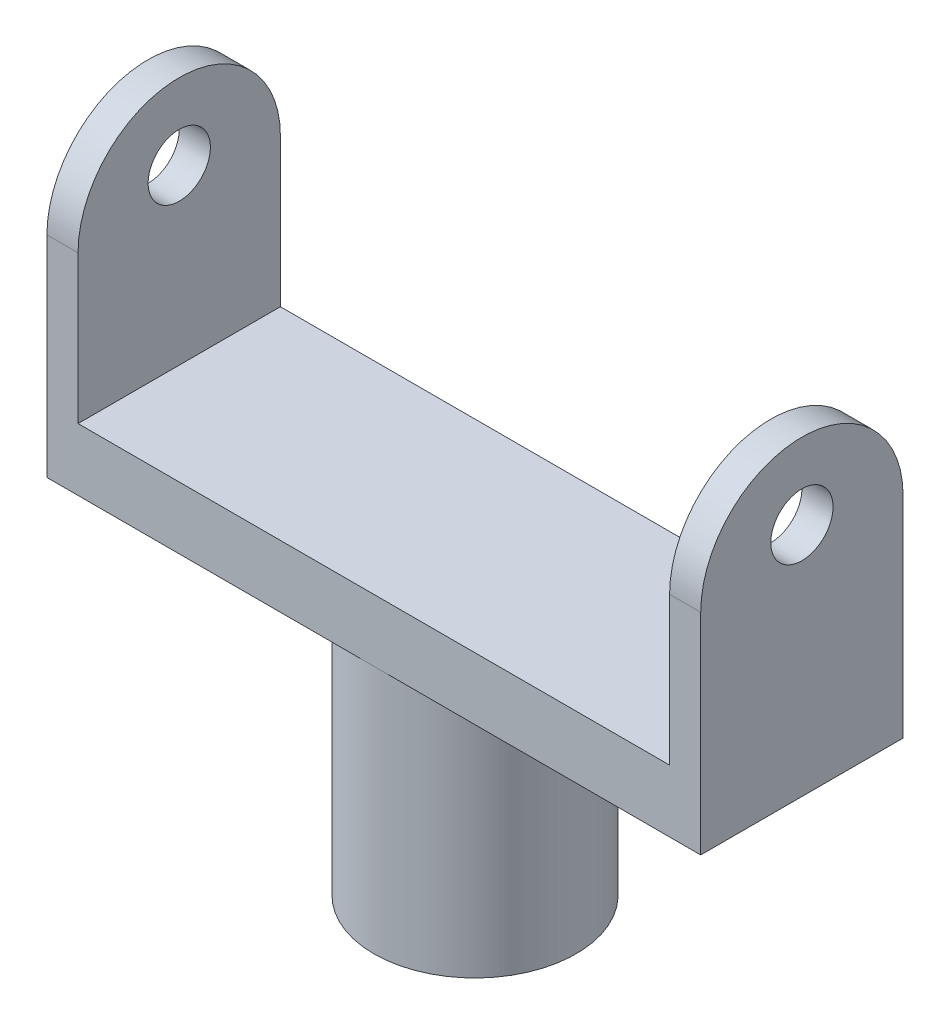
SolidWorks part; units mm, degrees
ref_plane "Front Plane" through (0, 0, 0) normal (0, 0, 1) x (1, 0, 0)
ref_plane "Top Plane" through (0, 0, 0) normal (0, 1, 0) x (1, 0, 0)
ref_plane "Right Plane" through (0, 0, 0) normal (1, 0, 0) x (0, 0, -1)
sketch "Sketch1" plane through (0, 0, 0) normal (0, 1, 0) x (1, 0, 0)
  circle A0 centre (0, 0) radius 2.75
  circle A1 centre (0, 0) radius 3.25
  dimension "D1" = 6.5
  dimension "D2" = 5.5
extrude "Boss-Extrude1" add sketch "Sketch1" along normal blind 8
sketch "Sketch2" plane through (0, 8, 0) normal (0, 1, 0) x (1, 0, 0)
  line L1 (-10.5, 3.25) -> (10.5, 3.25)
  line L2 (-10.5, 3.25) -> (-10.5, -3.25)
  line L3 (-10.5, -3.25) -> (10.5, -3.25)
  line L4 (10.5, 3.25) -> (10.5, -3.25)
  line L5 (-10.5, 3.25) -> (10.5, -3.25) construction
  line L6 (-10.5, -3.25) -> (10.5, 3.25) construction
  circle A1 centre (0, 0) radius 3.25 construction
  point P0 (0, 0)
  dimension "D1" = 21
  dimension "D2" = 21
extrude "Boss-Extrude2" add sketch "Sketch2" along normal blind 2
sketch "Sketch3" plane through (0, 10, 0) normal (0, 1, 0) x (1, 0, 0)
  line L0 (-10.5, -3.25) -> (10.5, -3.25) construction
  line L1 (-10.5, 3.25) -> (-9.5, 3.25)
  line L2 (-10.5, 3.25) -> (-10.5, -3.25)
  line L3 (-10.5, -3.25) -> (-9.5, -3.25)
  line L4 (-9.5, 3.25) -> (-9.5, -3.25)
  line L6 (10.5, 3.25) -> (9.5, 3.25)
  line L7 (10.5, 3.25) -> (10.5, -3.25)
  line L8 (10.5, -3.25) -> (9.5, -3.25)
  line L9 (9.5, 3.25) -> (9.5, -3.25)
  dimension "D1" = 1
  dimension "D2" = 1
extrude "Boss-Extrude3" add sketch "Sketch3" along normal blind 8
sketch "Sketch4" plane through (-10.5, 0, 0) normal (-1, 0, 0) x (0, 0, 1)
  line L0 (-3.25, 8) -> (3.25, 8) construction
  circle A0 centre (0, 15.56) radius 1
  dimension "D2" = 2
  dimension "D1" = 7.56
extrude "Cut-Extrude1" cut sketch "Sketch4" against normal through all both
fillet "Fillet1" 2 edges at (10, 18, 3.25) (10, 18, -3.25) type full round first side face at (0, 12.8889, 3.25) second side face at (0, 12.8889, -3.25) middle face at (10, 18, 0)
fillet "Fillet2" 2 edges at (-10, 18, 3.25) (-10, 18, -3.25) type full round first side face at (0, 12.1667, 3.25) second side face at (0, 12.1667, -3.25) middle face at (-10, 18, 0)
